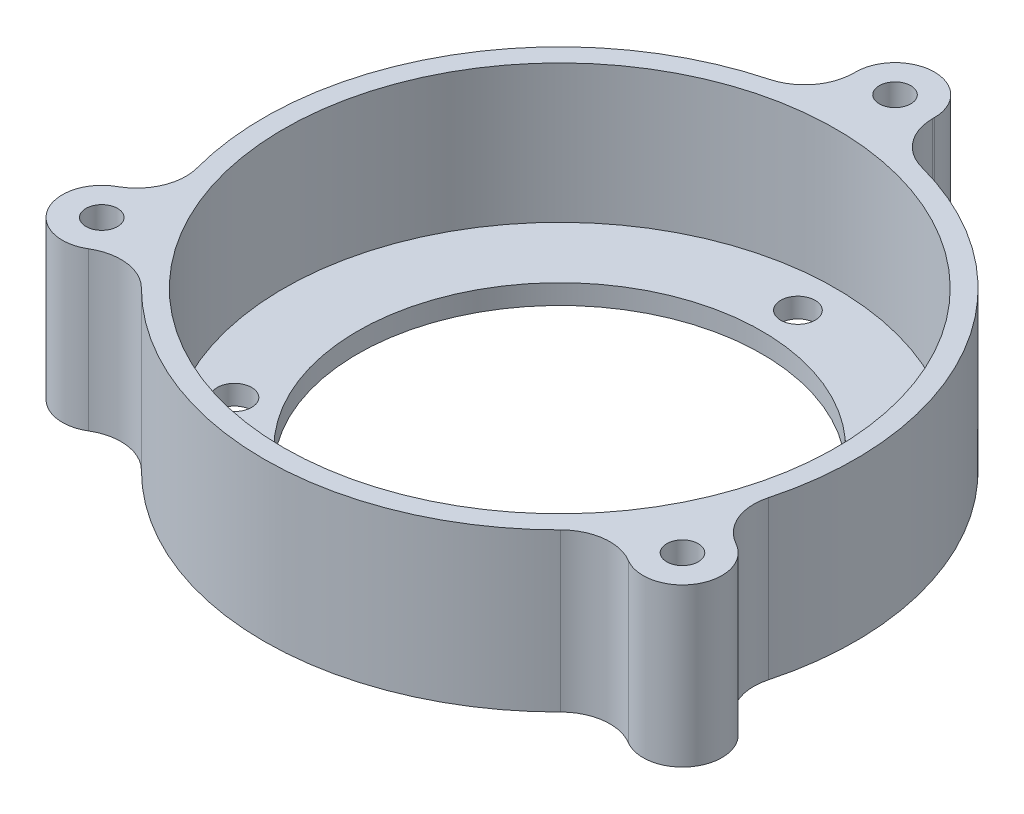
SolidWorks part; units mm, degrees
ref_plane "Front Plane" through (0, 0, 0) normal (0, 0, 1) x (1, 0, 0)
ref_plane "Top Plane" through (0, 0, 0) normal (0, 1, 0) x (1, 0, 0)
ref_plane "Right Plane" through (0, 0, 0) normal (1, 0, 0) x (0, 0, -1)
sketch "Sketch1" plane through (0, 0, 0) normal (0, 1, 0) x (1, 0, 0)
  circle A5 centre (0, 0) radius 20.5
  circle A6 centre (0, 0) radius 30
  dimension "D1" = 60
  dimension "D6" = 41
extrude "Boss-Extrude1" add sketch "Sketch1" along normal blind 16
sketch "Sketch2" plane through (0, 16, 0) normal (0, 1, 0) x (1, 0, 0)
  circle A0 centre (0, 0) radius 28
  dimension "D1" = 56
extrude "Cut-Extrude1" cut sketch "Sketch2" against normal offset from surface (14 mm away) 2 up to face at (0, 0, 30)
ref_axis "Axis1" through (0, -13.0663, 0) along (0, 1, 0)
sketch "Sketch3" plane through (0, 0, 0) normal (1, 0, 0) x (0, 0, -1)
  line L0 (0, -13.0663) -> (0, 19.0161) construction
  line L1 (30, 16) -> (-30, 16) construction
  circle A0 centre (0, 8) radius 1.1
  dimension "D2" = 2.2
  dimension "D1" = 8
sketch "Sketch4" plane through (0, 16, 0) normal (0, 1, 0) x (1, 0, 0)
  line L0 (-29.4449, -17) -> (0, 0) construction
  line L1 (0, 0) -> (29.4449, -17) construction
  line L2 (0, 0) -> (0, 34) construction
  line L3 (4, 34) -> (4, 29.7321)
  line L4 (-4, 34) -> (-4, 29.7321)
  line L5 (27.2446, -20.3405) -> (23.8975, -18.1358)
  line L6 (31.2376, -13.4242) -> (27.7461, -11.4084)
  line L7 (-27.2446, -20.3405) -> (-23.8975, -18.1358)
  line L8 (-31.4449, -13.5359) -> (-27.7488, -11.402)
  circle A0 centre (0, 0) radius 34 construction
  circle A1 centre (0, 34) radius 4
  circle A2 centre (29.4449, -17) radius 4
  circle A4 centre (0, 0) radius 30
  circle A5 centre (-29.4449, -17) radius 4
  circle A6 centre (0, 0) radius 30 construction
  circle A7 centre (-29.4449, -17) radius 1.6
  circle A8 centre (0, 34) radius 1.6
  circle A9 centre (29.4449, -17) radius 1.6
  circle M14 centre (0, 0) radius 30
  dimension "D3" = 8
  dimension "D4" = 3.2
  dimension "D1" = 120
  dimension "D2" = 120
extrude "Boss-Extrude2" add sketch "Sketch4" against normal up to surface (16 mm away) contours A5 A7 | A5 L7 A4 | A5 L8 M14 | A1 A8 | A1 L3 M14 | A1 L4 M14 | A2 L5 M14 | A2 L6 M14 | A2 A9 region at (2.7484, 16, -31.2516) region at (3.0966, 16, -30.8019) region at (-3.0966, 16, -30.8019) region at (28.2136, 16, 12.7214) region at (-28.2235, 16, 12.7192) region at (32.7523, 16, 14.9584) region at (25.1468, 16, 17.9486) region at (-28.4389, 16, 13.2456) region at (-25.1468, 16, 17.9486) up to face at (0, 0, 30)
fillet "Fillet1" radius 5 6 edges at (23.8975, 8, 18.1358) (27.7461, 8, 11.4084) (4, 8, -29.7321) (-4, 8, -29.7321) (-27.7488, 8, 11.402) (-23.8975, 8, 18.1358)
sketch "Sketch5" plane through (0, 2, 0) normal (0, 1, 0) x (1, 0, 0)
  line L0 (0, -1.1) -> (0, 1.1) construction
  line L2 (-20.915, -12.0753) -> (0, 24.1506) construction
  line L3 (0, 24.1506) -> (20.915, -12.0753) construction
  line L4 (20.915, -12.0753) -> (-20.915, -12.0753) construction
  circle A0 centre (0, 0) radius 24.1506 construction
  circle A1 centre (0, 24.1506) radius 1.75
  circle A2 centre (-20.915, -12.0753) radius 1.75
  circle A3 centre (20.915, -12.0753) radius 1.75
  dimension "D2" = 3.5
  dimension "D1" = 41.83
extrude "Cut-Extrude2" cut sketch "Sketch5" against normal through all
